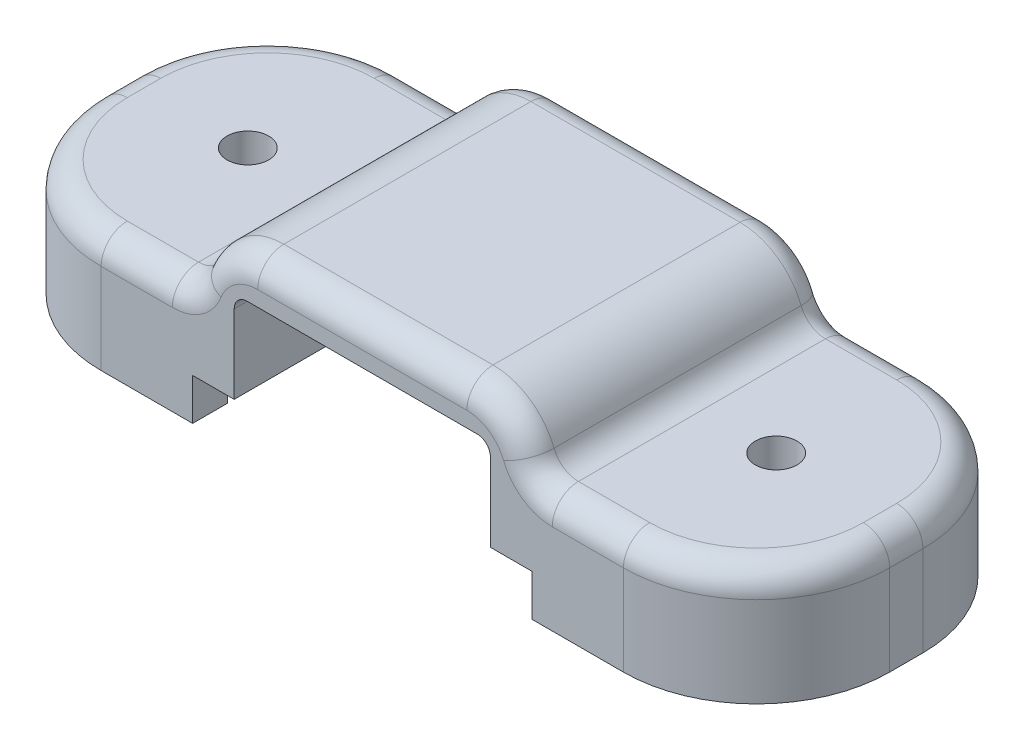
SolidWorks part; units mm, degrees
ref_plane "Front Plane" through (0, 0, 0) normal (0, 0, 1) x (1, 0, 0)
ref_plane "Top Plane" through (0, 0, 0) normal (0, 1, 0) x (1, 0, 0)
ref_plane "Right Plane" through (0, 0, 0) normal (1, 0, 0) x (0, 0, -1)
sketch "Sketch1" plane through (0, 0, 0) normal (0, 0, 1) x (1, 0, 0)
  line L0 (9.779, 17.145) -> (9.779, 13.97) construction
  line L1 (0, 0) -> (19.558, 0)
  line L2 (0, 0) -> (0, 13.97)
  line L3 (0, 13.97) -> (19.558, 13.97)
  line L4 (19.558, 0) -> (19.558, 13.97)
  line L5 (-3.175, 17.145) -> (22.733, 17.145)
  line L6 (-3.175, 17.145) -> (-3.175, -3.175)
  line L7 (-3.175, -3.175) -> (22.733, -3.175)
  line L8 (22.733, 17.145) -> (22.733, -3.175)
  line L9 (19.558, 6.985) -> (22.733, 6.985)
  line L10 (0, 6.985) -> (-3.175, 6.985)
  dimension "D1" = 13.97
  dimension "D2" = 19.558
  dimension "D3" = 3.175
extrude "Boss-Extrude1" add sketch "Sketch1" along normal blind 22.86 contours L5 L0 L3 L4 L9 L8 | L0 L5 L6 L10 L2 L3 region at (16.256, 16.9804, 0) region at (9.6144, 15.5575, 0)
sketch "Sketch2" plane through (-3.175, 0, 0) normal (-1, 0, 0) x (0, 0, 1)
  line L0 (0, 17.145) -> (0, 6.985) construction
  line L1 (0, 12.7) -> (22.86, 12.7)
  line L2 (0, 12.7) -> (0, 6.985)
  line L3 (0, 6.985) -> (22.86, 6.985) construction
  line L4 (22.86, 12.7) -> (22.86, 6.985)
  line L6 (0, 6.985) -> (22.86, 6.985)
  line L7 (0, 6.985) -> (0, 3.81)
  line L8 (0, 3.81) -> (22.86, 3.81)
  line L9 (22.86, 6.985) -> (22.86, 3.81)
  line M2 (0, 17.145) -> (0, 6.985)
  line M3 (0, 6.985) -> (22.86, 6.985)
  line M4 (22.86, 6.985) -> (22.86, 17.145)
  dimension "D1" = 5.715
  dimension "D2" = 3.175
extrude "Boss-Extrude2" add sketch "Sketch2" along normal blind 17.145 contours L1 M2 M3 M4 | L9 L7 L8 M3 region at (-3.175, 9.8425, 11.43) region at (-3.175, 5.3975, 11.43)
sketch "Sketch3" plane through (22.733, 0, 0) normal (1, 0, 0) x (0, 0, -1)
  line L0 (0, 17.145) -> (0, 6.985) construction
  line L1 (-22.86, 6.985) -> (0, 6.985) construction
  line L2 (-22.86, 6.985) -> (-22.86, 12.7)
  line L3 (-22.86, 12.7) -> (0, 12.7)
  line L4 (0, 6.985) -> (0, 12.7)
  line L5 (0, 6.985) -> (0, 3.81) construction
  line L6 (-22.86, 6.985) -> (0, 6.985) construction
  line L7 (-22.86, 6.985) -> (-22.86, 3.81)
  line L8 (-22.86, 3.81) -> (0, 3.81)
  line L9 (0, 6.985) -> (0, 3.81)
  line M3 (0, 6.985) -> (0, 17.145)
  line M5 (-22.86, 17.145) -> (-22.86, 6.985)
  line M6 (-22.86, 6.985) -> (0, 6.985)
  dimension "D1" = 5.715
  dimension "D2" = 3.175
extrude "Boss-Extrude3" add sketch "Sketch3" along normal blind 17.145 contours L3 M5 M6 M3 | L9 L7 L8 M6 region at (22.733, 5.3975, 11.43) region at (22.733, 9.8425, 11.43)
sketch "Sketch4" plane through (22.733, 0, 0) normal (-1, 0, 0) x (0, 0, 1)
  line L0 (22.86, 6.985) -> (0, 6.985) construction
  line L1 (2.675, 6.985) -> (20.185, 6.985)
  line L2 (2.675, 6.985) -> (2.675, 3.81)
  line L3 (2.675, 3.81) -> (20.185, 3.81)
  line L4 (20.185, 6.985) -> (20.185, 3.81)
  line L5 (22.86, 3.81) -> (0, 3.81) construction
  line L6 (2.675, 5.3975) -> (0, 5.3975) construction
  line L7 (0, 3.81) -> (0, 6.985) construction
  line L8 (20.185, 5.3975) -> (22.86, 5.3975) construction
  line L9 (22.86, 6.985) -> (22.86, 3.81) construction
  dimension "D1" = 2.675
extrude "Cut-Extrude1" cut sketch "Sketch4" against normal blind 13.97
sketch "Sketch5" plane through (-3.175, 0, 0) normal (1, 0, 0) x (0, 0, -1)
  line L0 (-22.86, 6.985) -> (0, 6.985) construction
  line L1 (-20.185, 6.985) -> (-2.675, 6.985)
  line L2 (-20.185, 6.985) -> (-20.185, 3.81)
  line L3 (-20.185, 3.81) -> (-2.675, 3.81)
  line L4 (-2.675, 6.985) -> (-2.675, 3.81)
  line L5 (0, 3.81) -> (-22.86, 3.81) construction
  line L6 (-20.185, 5.3975) -> (-22.86, 5.3975) construction
  line L7 (-22.86, 3.81) -> (-22.86, 6.985) construction
  line L8 (-2.675, 5.3975) -> (0, 5.3975) construction
  line L9 (0, 6.985) -> (0, 3.81) construction
  dimension "D2" = 2.675
extrude "Cut-Extrude2" cut sketch "Sketch5" against normal blind 13.97
sketch "Sketch6" plane through (0, 12.7, 0) normal (0, 1, 0) x (1, 0, 0)
  line L0 (-10.3886, -11.43) -> (-3.175, -11.43) construction
  line L3 (-3.175, 0) -> (-3.175, -22.86) construction
  line L6 (-3.175, -11.43) -> (22.733, -11.43) construction
  line L9 (22.733, -22.86) -> (22.733, 0) construction
  line L12 (22.733, -11.43) -> (29.9466, -11.43) construction
  circle A0 centre (29.9466, -11.43) radius 1.5875
  circle A1 centre (-10.3886, -11.43) radius 1.5875
  point P25 (29.9466, -11.43)
  dimension "D1" = 40.3352
  dimension "D3" = 3.175
  dimension "D4" = 3.175
extrude "Cut-Extrude3" cut sketch "Sketch6" against normal blind 8.89
fillet "Fillet1" radius 8.255 4 edges at (-17.145, 5.3975, 20.185) (-17.145, 5.3975, 2.675) (36.703, 5.3975, 2.675) (36.703, 5.3975, 20.185)
fillet "Fillet2" radius 10.16 4 edges at (-20.32, 8.255, 22.86) (-20.32, 8.255, 0) (39.878, 8.255, 22.86) (39.878, 8.255, 0)
fillet "Fillet3" radius 1 2 edges at (19.558, 13.97, 11.43) (0, 13.97, 11.43)
fillet "Fillet4" radius 5 2 edges at (22.733, 17.145, 11.43) (-3.175, 17.145, 11.43)
fillet "Fillet5" radius 2 18 edges at (9.779, 17.145, 0) (9.779, 17.145, 22.86) (36.9022, 12.7, 19.8842) (39.878, 12.7, 11.43) (-17.3442, 12.7, 19.8842) (-20.32, 12.7, 11.43) (36.9022, 12.7, 2.9758) (-17.3442, 12.7, 2.9758)
